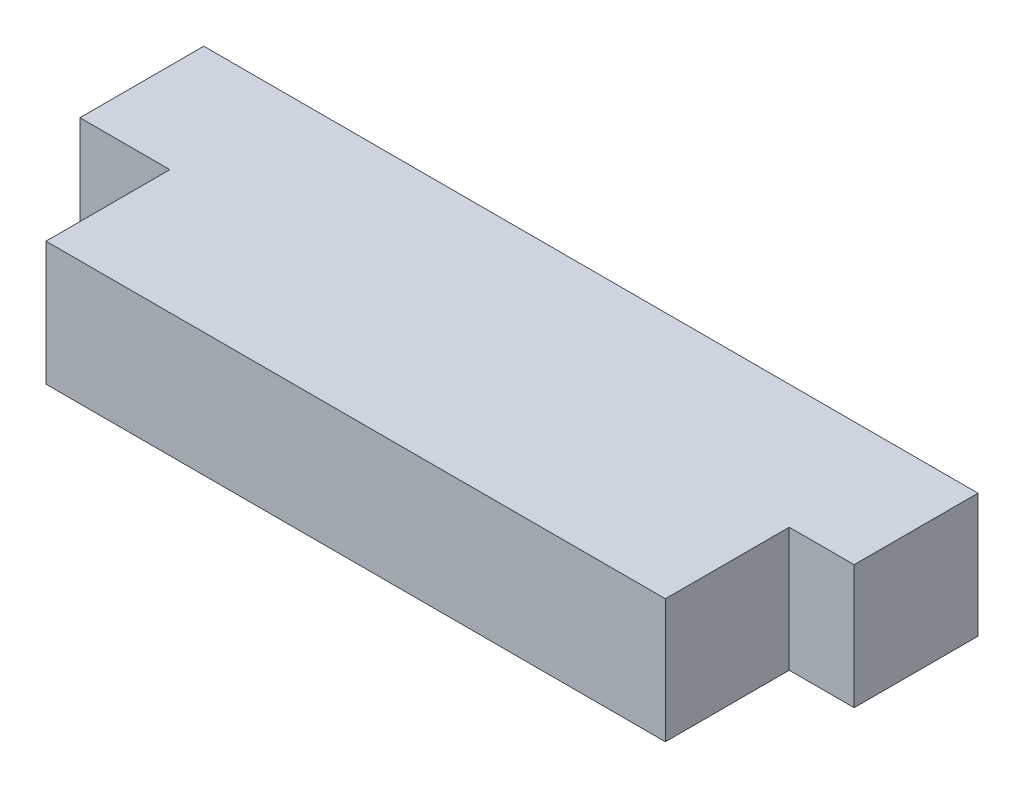
SolidWorks part; units mm, degrees
ref_plane "Front Plane" through (0, 0, 0) normal (0, 0, 1) x (1, 0, 0)
ref_plane "Top Plane" through (0, 0, 0) normal (0, 1, 0) x (1, 0, 0)
ref_plane "Right Plane" through (0, 0, 0) normal (1, 0, 0) x (0, 0, -1)
sketch "Sketch1" plane through (0, 0, 0) normal (0, 1, 0) x (1, 0, 0)
  line L0 (22.9049, 0) -> (25, 0)
  line L1 (0, 0) -> (2.9049, 0)
  line L2 (0, 0) -> (0, 4)
  line L3 (0, 4) -> (25, 4)
  line L4 (25, 0) -> (25, 4)
  line L6 (2.9049, 0) -> (2.9049, -4)
  line L7 (2.9049, -4) -> (22.9049, -4)
  line L8 (22.9049, 0) -> (22.9049, -4)
  dimension "D1" = 20
  dimension "D2" = 25
  dimension "D3" = 4
  dimension "D4" = 4
extrude "Boss-Extrude1" add sketch "Sketch1" along normal blind 4
